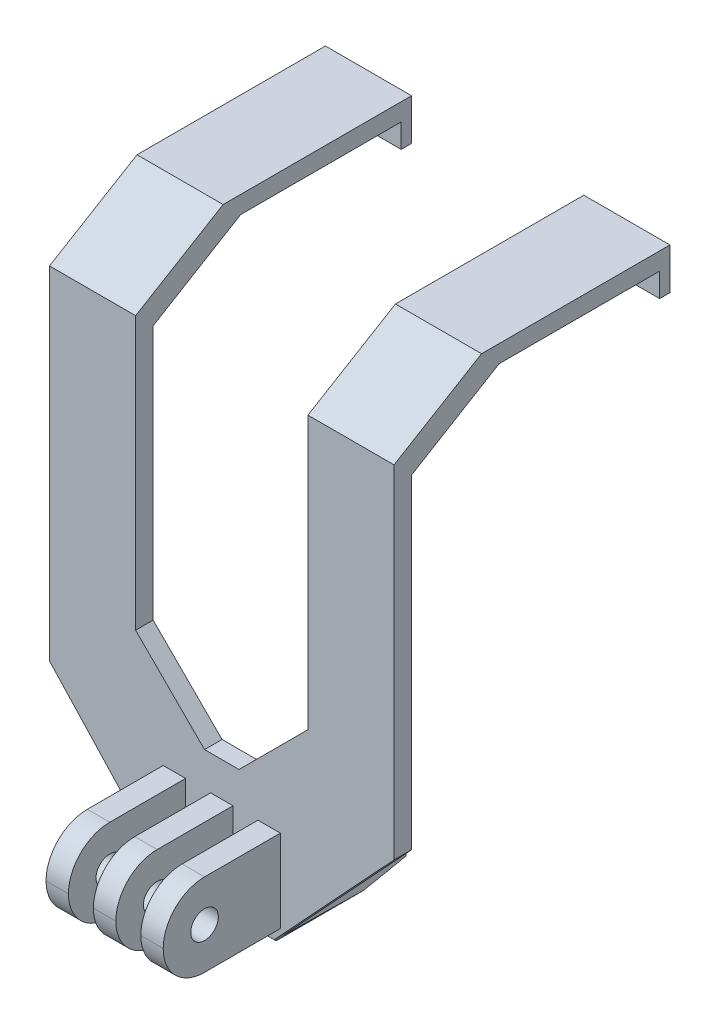
SolidWorks part; units mm, degrees
ref_plane "Front Plane" through (0, 0, 0) normal (0, 0, 1) x (1, 0, 0)
ref_plane "Top Plane" through (0, 0, 0) normal (0, 1, 0) x (1, 0, 0)
ref_plane "Right Plane" through (0, 0, 0) normal (1, 0, 0) x (0, 0, -1)
sketch "Sketch1" plane through (0, 0, 0) normal (1, 0, 0) x (0, 0, -1)
  line L0 (2.54, 77.46) -> (38.54, 77.46)
  line L1 (38.54, 77.46) -> (38.54, 74)
  line L2 (40.04, 74) -> (40.04, 80)
  line L3 (38.54, 74) -> (40.04, 74)
  line L4 (40.04, 80) -> (0, 80)
  line L5 (0, 80) -> (0, 0)
  line L6 (0, 0) -> (24.04, 0)
  line L7 (24.04, 0) -> (24.04, 5.04)
  line L8 (24.04, 5.04) -> (22.54, 5.04)
  line L9 (22.54, 5.04) -> (22.54, 2.54)
  line L10 (22.54, 2.54) -> (2.54, 2.54)
  line L11 (2.54, 2.54) -> (2.54, 77.46)
  dimension "D1" = 36
  dimension "D2" = 2.54
  dimension "D3" = 1.5
  dimension "D4" = 2.54
  dimension "D5" = 2.54
  dimension "D6" = 80
  dimension "D7" = 20
  dimension "D8" = 1.5
  dimension "D9" = 2.5
  dimension "D11" = 6
extrude "Boss-Extrude1" add sketch "Sketch1" along normal mid plane 50
chamfer "Chamfer1" distance 7.62 distance2 12.7 1 edges at (0, 77.46, -2.54) first distance on face at (0, 40, -2.54)
chamfer "Chamfer2" distance 12.7 distance2 7.62 1 edges at (0, 80, 0) first distance on face at (0, 80, -20.02)
sketch "Sketch2" plane through (0, 0, 0) normal (0, 0, 1) x (1, 0, 0)
  line L0 (0, 0) -> (0, 100.9862) construction
  line L1 (-12.5, 87.9388) -> (12.5, 87.9388)
  line L6 (12.5, 87.9388) -> (12.5, 22.8477)
  line L7 (-12.5, 87.9388) -> (-12.5, 22.8477)
  line L8 (12.5, 22.8477) -> (-12.5, 22.8477)
  line L9 (25, 22.7337) -> (3.8906, 0)
  line L10 (25, 72.38) -> (25, 0) construction
  line L11 (25, 0) -> (-25, 0) construction
  line L12 (-25, 22.7337) -> (-3.8906, 0)
  line L13 (3.8906, 0) -> (3.8906, -6.2257)
  line L14 (-3.8906, 0) -> (-3.8906, -6.2257)
  line L15 (3.8906, -6.2257) -> (33.5801, -6.2257)
  line L16 (-3.8906, -6.2257) -> (-33.5801, -6.2257)
  line L17 (33.5801, -6.2257) -> (33.5801, 22.7337)
  line L18 (-33.5801, -6.2257) -> (-33.5801, 22.7337)
  line L19 (33.5801, 22.7337) -> (25, 22.7337)
  line L20 (-33.5801, 22.7337) -> (-25, 22.7337)
  point P6 (0, 87.9388)
  point P9 (0, 22.8477)
  line M7 (25, 0) -> (25, 72.38)
  line M8 (25, 72.38) -> (-25, 72.38)
  line M10 (-25, 0) -> (25, 0)
  dimension "D1" = 25
extrude "Cut-Extrude1" cut sketch "Sketch2" against normal through all contours L17 L19 L13 L15 M7 M10 | L9 M7 M10 | L8 L0 L7 M8 | L0 L8 L6 M8 | L0 L6 L1 M8 | L0 L1 L7 M8 | L20 L12 L14 L16 L18 region at (-6.25, 47.6138, 0) region at (6.25, 47.6138, 0) region at (14.4453, -0.4147, 0) region at (17.9635, 7.5779, 0) region at (-6.25, 80.1594, 0) region at (6.25, 80.1594, 0)
chamfer "Chamfer3" distance 10 angle 45 2 edges at (12.5, 22.8477, -1.27) (-12.5, 22.8477, -1.27)
sketch "Sketch3" plane through (0, 0, 0) normal (0, -1, 0) x (1, 0, 0)
  line L0 (0, 2.354) -> (0, -29.7315) construction
  line L1 (6.2491, -2.54) -> (2.0925, -27.478)
  line L2 (-6.2491, -2.54) -> (-2.0925, -27.478)
  line L3 (2.0925, -27.478) -> (-2.0925, -27.478)
  line L4 (6.2491, -2.54) -> (9.0676, -2.54)
  line L5 (25, -2.54) -> (6.2491, -2.54) construction
  line L6 (-6.2491, -2.54) -> (-9.0676, -2.54)
  line L7 (9.0676, -2.54) -> (9.0676, -35.3116)
  line L8 (-9.0676, -2.54) -> (-9.0676, -35.3116)
  line L9 (9.0676, -35.3116) -> (-9.0676, -35.3116)
  point P8 (0, -27.478)
  point P15 (0, -35.3116)
extrude "Cut-Extrude2" cut sketch "Sketch3" against normal blind 10
chamfer "Chamfer4" distance 4 angle 45 2 edges at (0, 0, 0) (0, 2.54, -2.54)
sketch "Sketch4" plane through (0, 0, 0) normal (0, 0, 1) x (1, 0, 0)
  line L0 (0, 0) -> (0, 43.2355) construction
  line L1 (-8.5, 17.8477) -> (8.5, 17.8477)
  line L2 (8.5, 17.8477) -> (8.5, 5.8477)
  line L3 (-8.5, 17.8477) -> (-8.5, 5.8477)
  line L4 (8.5, 5.8477) -> (-8.5, 5.8477)
  line L5 (2.5, 22.8477) -> (-2.5, 22.8477) construction
  line L6 (-5.25, 17.8477) -> (-5.25, 5.8477)
  line L7 (5.25, 17.8477) -> (8.5, 17.8477)
  line L8 (5.25, 17.8477) -> (5.25, 5.8477)
  line L9 (5.25, 5.8477) -> (8.5, 5.8477)
  line L10 (8.5, 17.8477) -> (8.5, 5.8477)
  line L11 (-5.25, 17.8477) -> (-8.5, 17.8477)
  line L12 (-8.5, 17.8477) -> (-8.5, 5.8477)
  line L13 (-5.25, 5.8477) -> (-8.5, 5.8477)
  line L14 (-1.625, 17.8477) -> (1.625, 17.8477)
  line L15 (1.625, 17.8477) -> (1.625, 5.8477)
  line L16 (-1.625, 17.8477) -> (-1.625, 5.8477)
  line L17 (1.625, 5.8477) -> (-1.625, 5.8477)
  point P6 (0, 17.8477)
  point P8 (0, 5.8477)
  point P19 (0, 17.8477)
  point P21 (0, 5.8477)
  dimension "D1" = 17
  dimension "D2" = 5
  dimension "D3" = 3.25
  dimension "D4" = 3.25
  dimension "D5" = 12
extrude "Boss-Extrude2" add sketch "Sketch4" along normal blind 17 contours L6 L1 L3 L4 | L0 L4 L15 L14 | L17 L0 L1 L16 | L1 L8 L4 L2 region at (-0.8125, 11.8477, 0) region at (0.8125, 11.8477, 0) region at (6.875, 11.8477, 0) region at (-6.875, 11.8477, 0)
fillet "Fillet1" radius 6 6 edges at (-6.875, 5.8477, 17) (0, 5.8477, 17) (6.875, 5.8477, 17) (6.875, 17.8477, 17) (0, 17.8477, 17) (-6.875, 17.8477, 17)
sketch "Sketch5" plane through (8.5, 0, 0) normal (1, 0, 0) x (0, 0, -1)
  line L0 (-11, 17.8477) -> (-11, 5.8477) construction
  circle A0 centre (-11, 11.8477) radius 2
  point P3 (-11, 11.8477)
  point P6 (-11, 11.8477)
  point P11 (-11, 11.8477)
  dimension "D1" = 4
extrude "Cut-Extrude3" cut sketch "Sketch5" against normal through all contours A0
